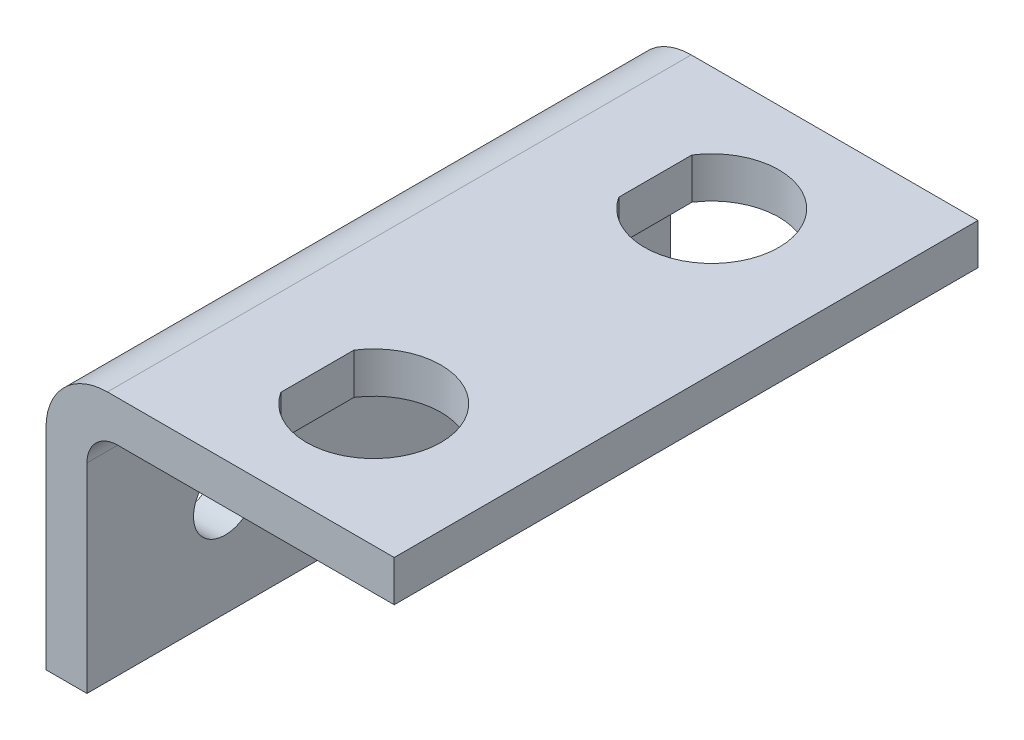
SolidWorks part; units mm, degrees
ref_plane "Front Plane" through (0, 0, 0) normal (0, 0, 1) x (1, 0, 0)
ref_plane "Top Plane" through (0, 0, 0) normal (0, 1, 0) x (1, 0, 0)
ref_plane "Right Plane" through (0, 0, 0) normal (1, 0, 0) x (0, 0, -1)
sketch "Sketch1" plane through (0, 0, 0) normal (0, 0, 1) x (1, 0, 0)
  line L0 (-1, 0) -> (1, 0) construction
  line L1 (1, 0) -> (1, 7.75)
  line L2 (-1, 0) -> (-1, 8.25)
  line L3 (2.5, 9.25) -> (14, 9.25)
  line L4 (14, 9.25) -> (14, 11.25) construction
  line L5 (14, 11.25) -> (2, 11.25)
  line L6 (14, 11.25) -> (16, 11.25)
  line L7 (16, 11.25) -> (16, 9.25)
  line L8 (16, 9.25) -> (14, 9.25)
  line L9 (-1, 0) -> (-1, -2)
  line L10 (-1, -2) -> (1, -2)
  line L11 (1, -2) -> (1, 0)
  arc A0 (2.5, 9.25) -> (1, 7.75) centre (2.5, 7.75) ccw
  arc A1 (2, 11.25) -> (-1, 8.25) centre (2, 8.25) ccw
  dimension "D2" = 3
  dimension "D3" = 1.5
  dimension "D1" = 2
  dimension "D4" = 15
  dimension "D5" = 2
  dimension "D6" = 11.25
  dimension "D7" = 2
  dimension "D8" = 2
extrude "Boss-Extrude1" add sketch "Sketch1" along normal blind 14.25 and the other way blind 14.25
sketch "Sketch2" plane through (0, 11.25, 0) normal (0, 1, 0) x (1, 0, 0)
  line L0 (6.2482, -10.035) -> (6.2482, -6.465)
  line L1 (6.2482, 6.465) -> (6.2482, 10.035)
  line L3 (9, -14.25) -> (9, 14.25) construction
  line L4 (16, -14.25) -> (2, -14.25) construction
  line L5 (16, 14.25) -> (2, 14.25) construction
  line L6 (9, 8.25) -> (9, -8.25) construction
  line L9 (14, 14.25) -> (14, -14.25) construction
  line L10 (16, 14.25) -> (2, 14.25) construction
  line L11 (16, -14.25) -> (2, -14.25) construction
  line L12 (16, 14.25) -> (16, -14.25) construction
  circle A0 centre (9, 8.25) radius 3.28 construction
  circle A1 centre (9, -8.25) radius 3.28 construction
  arc A2 (6.2482, 10.035) -> (6.2482, 6.465) centre (9, 8.25) cw
  arc A3 (6.2482, -6.465) -> (6.2482, -10.035) centre (9, -8.25) cw
  point P14 (9, 0)
  dimension "D1" = 6.56
  dimension "D2" = 6.56
  dimension "D3" = 3.57
  dimension "D4" = 3.57
  dimension "D5" = 2
  dimension "D6" = 16.5
  dimension "D7" = 5
extrude "Cut-Extrude1" cut sketch "Sketch2" against normal up to next
sketch "Sketch3" plane through (1, 0, 0) normal (1, 0, 0) x (0, 0, -1)
  line L1 (-14.25, 2.875) -> (14.25, 2.875) construction
  line L2 (-14.25, -2) -> (-14.25, 7.75) construction
  line L3 (14.25, -2) -> (14.25, 7.75) construction
  line L4 (0, -2) -> (0, 7.75) construction
  line L5 (14.25, -2) -> (-14.25, -2) construction
  line L6 (14.25, 7.75) -> (-14.25, 7.75) construction
  line L7 (-7.5, 2.875) -> (7.5, 2.875) construction
  circle A0 centre (-7.5, 2.875) radius 1.55
  circle A1 centre (7.5, 2.875) radius 1.55
  point P16 (0, 2.875)
  dimension "D1" = 3.1
  dimension "D2" = 3.1
  dimension "D3" = 15
extrude "Cut-Extrude2" cut sketch "Sketch3" against normal up to next
